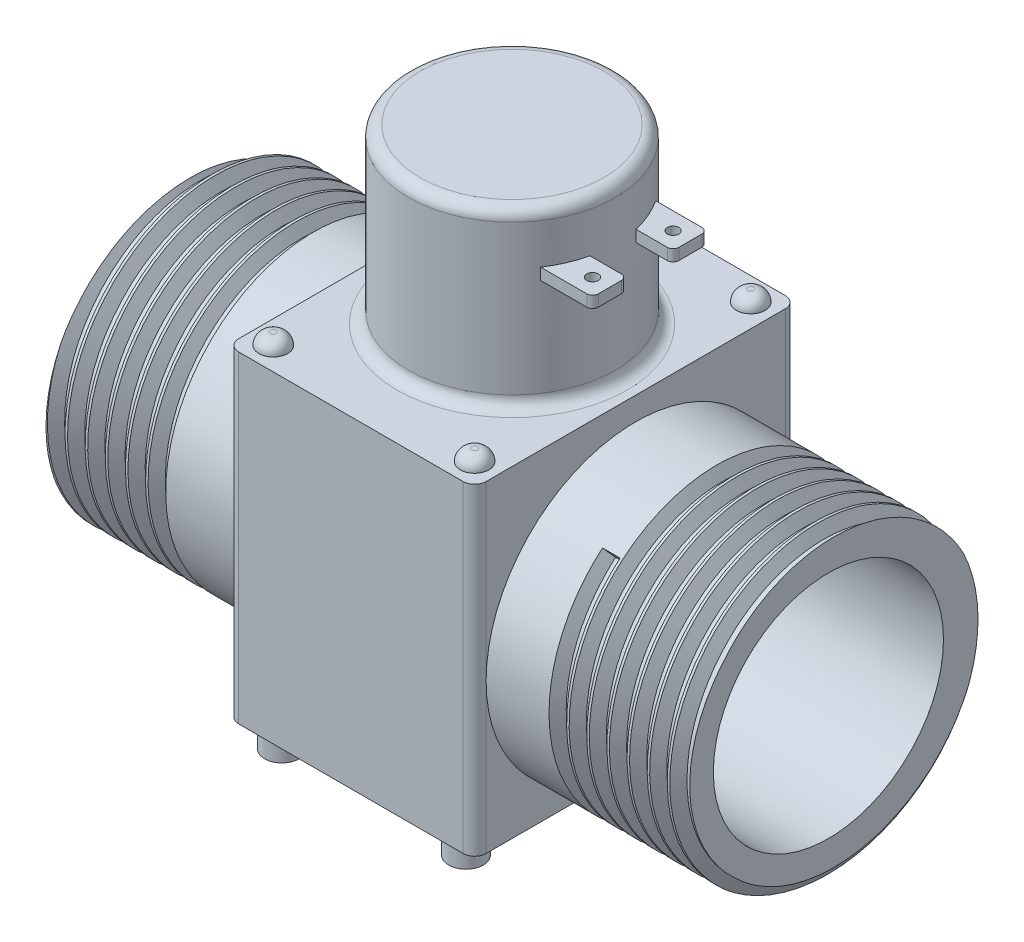
SolidWorks part; units mm, degrees
material "PVC rigide"
ref_plane "Plan de face" through (0, 0, 0) normal (0, 0, 1) x (1, 0, 0)
ref_plane "Plan de dessus" through (0, 0, 0) normal (0, 1, 0) x (1, 0, 0)
ref_plane "Plan de droite" through (0, 0, 0) normal (1, 0, 0) x (0, 0, -1)
sketch "Esquisse2" plane through (0, 0, 0) normal (1, 0, 0) x (0, 0, -1)
  circle A0 centre (0, 0) radius 13
  dimension "D1" = 26
extrude "Boss.-Extru.1" add sketch "Esquisse2" along normal mid plane 60
thread "Filetage1" pitch 1.75 method cut profile "Profil de filetage1" start angle 0, offset 0, length 12.5, pitch 1.75, diameter 26
ref_plane "Plan1" through (-30, 0, -13) normal (0, -1, 0) x (0, 0, -1)
sketch "Profil de filetage1" plane through (-30, 0, -13) normal (0, -1, 0) x (0, 0, -1)
  line L0 (0, 0) -> (0, 1.75) construction
  line L11 (0, 0) -> (0, 1.5312)
  line L12 (0, 1.5312) -> (-0.9472, 0.9844)
  line L13 (-0.9472, 0.9844) -> (-0.9472, 0.5469)
  line L15 (-0.9472, 0.5469) -> (0, 0)
  line L17 (-0.9472, 0.7656) -> (0, 0.7656) construction
  point P2 (0, 0)
  dimension "Pitch" = 1.75
  dimension "Profile_Angle" = 60
  dimension "Profile_Land" = 0.4375
  dimension "Profile_Height" = 0.9472
sketch "Esquisse5" plane through (-30, 0, 0) normal (-1, 0, 0) x (0, 0, 1)
  circle A0 centre (0, 0) radius 13.5
  dimension "D1" = 27
extrude "Enlèv. mat.-Extru.1" cut sketch "Esquisse5" against normal blind 2.5
thread "Filetage2" pitch 1.75 method cut profile "Profil de filetage2" start angle 0, offset 0, length 12.5, pitch 1.75, diameter 26
ref_plane "Plan2" through (30, 0, 13) normal (0, -1, 0) x (0, 0, 1)
sketch "Profil de filetage2" plane through (30, 0, 13) normal (0, -1, 0) x (0, 0, 1)
  line L0 (0, 0) -> (0, 1.75) construction
  line L11 (0, 0) -> (0, 1.5312)
  line L12 (0, 1.5312) -> (-0.9472, 0.9844)
  line L13 (-0.9472, 0.9844) -> (-0.9472, 0.5469)
  line L15 (-0.9472, 0.5469) -> (0, 0)
  line L17 (-0.9472, 0.7656) -> (0, 0.7656) construction
  point P2 (0, 0)
  dimension "Pitch" = 1.75
  dimension "Profile_Angle" = 60
  dimension "Profile_Land" = 0.4375
  dimension "Profile_Height" = 0.9472
sketch "Esquisse8" plane through (30, 0, 0) normal (1, 0, 0) x (0, 0, -1)
  circle A0 centre (0, 0) radius 13.5
  dimension "D1" = 27
extrude "Enlèv. mat.-Extru.2" cut sketch "Esquisse8" against normal blind 2.5
sketch "Esquisse10" plane through (0, 0, 0) normal (0, 1, 0) x (1, 0, 0)
  line L1 (-10.75, 14) -> (10.75, 14)
  line L2 (-10.75, 14) -> (-10.75, -14)
  line L3 (-10.75, -14) -> (10.75, -14)
  line L4 (10.75, 14) -> (10.75, -14)
  line L5 (-10.75, 14) -> (10.75, -14) construction
  line L6 (-10.75, -14) -> (10.75, 14) construction
  point P0 (0, 0)
  dimension "D1" = 21.5
  dimension "D2" = 28
extrude "Boss.-Extru.2" add sketch "Esquisse10" along normal mid plane 30
sketch "Esquisse11" plane through (0, 15, 0) normal (0, 1, 0) x (1, 0, 0)
  circle A0 centre (0, 0) radius 9
  dimension "D1" = 18
extrude "Boss.-Extru.3" add sketch "Esquisse11" along normal blind 15
sketch "Esquisse12" plane through (0, -15, 0) normal (0, -1, 0) x (1, 0, 0)
  line L1 (-8, -12) -> (8, -12)
  line L2 (-8, -12) -> (-8, 12)
  line L3 (-8, 12) -> (8, 12)
  line L4 (8, -12) -> (8, 12)
  line L5 (-8, -12) -> (8, 12) construction
  line L6 (-8, 12) -> (8, -12) construction
  line L9 (-10.75, 14) -> (10.75, 14)
  line L10 (-10.75, 14) -> (-10.75, -14)
  line L11 (-10.75, -14) -> (10.75, -14)
  line L12 (10.75, 14) -> (10.75, -14)
  line L13 (-10.75, 14) -> (10.75, -14) construction
  line L14 (-10.75, -14) -> (10.75, 14) construction
  circle A0 centre (-8, 12) radius 1.5
  circle A1 centre (8, 12) radius 1.5
  circle A2 centre (8, -12) radius 1.5
  circle A3 centre (-8, -12) radius 1.5
  point P8 (0, 0)
  point P18 (0, 0)
  line M13 (10.75, -14) -> (10.75, 14)
  line M14 (10.75, 14) -> (-10.75, 14)
  line M15 (-10.75, 14) -> (-10.75, -14)
  line M16 (-10.75, -14) -> (10.75, -14)
  dimension "D3" = 3
  dimension "D4" = 3
  dimension "D5" = 3
  dimension "D6" = 3
  dimension "D1" = 24
  dimension "D2" = 16
extrude "Enlèv. mat.-Extru.4" cut sketch "Esquisse12" against normal blind 2 contours A3 L2 A0 L3 A1 L4 A2 L1 M16 M13 M14 M15 region at (0, -15, 13.647)
fillet "Congé1" radius 1 4 edges at (10.75, 1, -14) (-10.75, 1, -14) (-10.75, 1, 14) (10.75, 1, 14)
fillet "Congé2" radius 1 1 edges at (0, 15, 9)
fillet "Congé3" radius 1 1 edges at (0, 30, 9)
sketch "Esquisse9" plane through (-27.5, 0, 0) normal (-1, 0, 0) x (0, 0, 1)
  circle A0 centre (0, 0) radius 10
  dimension "D1" = 20
extrude "Enlèv. mat.-Extru.3" cut sketch "Esquisse9" against normal through all
sketch "Esquisse13" plane through (0, 15, 0) normal (0, 1, 0) x (1, 0, 0)
  line L1 (-8.75, -12) -> (8.75, -12) construction
  line L2 (-8.75, -12) -> (-8.75, 12) construction
  line L3 (-8.75, 12) -> (8.75, 12) construction
  line L4 (8.75, -12) -> (8.75, 12) construction
  line L5 (-8.75, -12) -> (8.75, 12) construction
  line L6 (-8.75, 12) -> (8.75, -12) construction
  circle A0 centre (-8.75, 12) radius 1.25
  circle A1 centre (8.75, 12) radius 1.25
  circle A2 centre (8.75, -12) radius 1.25
  circle A3 centre (-8.75, -12) radius 1.25
  point P8 (0, 0)
  dimension "D3" = 2.5
  dimension "D1" = 17.5
  dimension "D2" = 24
extrude "Boss.-Extru.4" add sketch "Esquisse13" along normal blind 1
fillet "Congé4" radius 1 4 edges at (8.75, 16, -10.75) (-8.75, 16, -10.75) (8.75, 16, 13.25) (-8.75, 16, 13.25)
ref_plane "Plan3" through (0, 25, 0) normal (0, 1, 0) x (1, 0, 0)
sketch "Esquisse14" plane through (0, 25, 0) normal (0, 1, 0) x (1, 0, 0)
  line L0 (-6.5449, 0) -> (6.8479, 0) construction
  line L1 (5.9995, 5) -> (11.4995, 5)
  line L2 (5.9995, 5) -> (5.9995, 2)
  line L3 (5.9995, 2) -> (11.4995, 2)
  line L4 (11.9995, 4.5) -> (11.9995, 2.5)
  line L5 (5.9995, -2) -> (11.4995, -2)
  line L6 (11.9995, -4.5) -> (11.9995, -2.5)
  line L7 (5.9995, -5) -> (11.4995, -5)
  line L8 (5.9995, -5) -> (5.9995, -2)
  circle A1 centre (10.4995, 3.5) radius 0.5
  arc A2 (11.4995, 5) -> (11.9995, 4.5) centre (11.4995, 4.5) cw
  arc A3 (11.4995, 2) -> (11.9995, 2.5) centre (11.4995, 2.5) ccw
  arc A4 (11.4995, -2) -> (11.9995, -2.5) centre (11.4995, -2.5) cw
  arc A5 (11.4995, -5) -> (11.9995, -4.5) centre (11.4995, -4.5) ccw
  circle A6 centre (10.4995, -3.5) radius 0.5
  point P9 (10.532, 3.219)
  point P10 (11.9995, 3.5)
  point P13 (11.9995, 5)
  point P16 (11.9995, 2)
  dimension "D4" = 1
  dimension "D6" = 2
  dimension "D7" = 0.5
  dimension "D1" = 5.9995
  dimension "D2" = 6
  dimension "D3" = 3
  dimension "D5" = 1.5
extrude "Boss.-Extru.5" add sketch "Esquisse14" against normal mid plane 1
